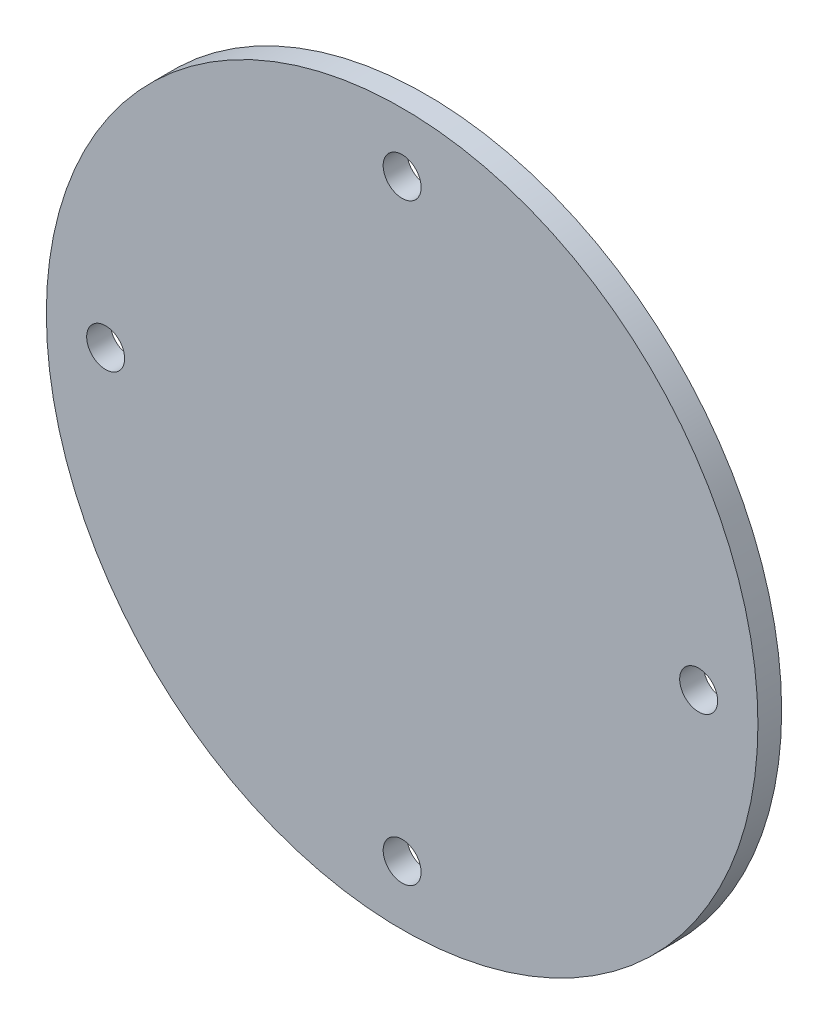
SolidWorks part; units mm, degrees
ref_plane "前视基准面" through (0, 0, 0) normal (0, 0, 1) x (1, 0, 0)
ref_plane "上视基准面" through (0, 0, 0) normal (0, 1, 0) x (1, 0, 0)
ref_plane "右视基准面" through (0, 0, 0) normal (1, 0, 0) x (0, 0, -1)
sketch "草图3" plane through (0, 0, 0) normal (0, 0, 1) x (1, 0, 0)
  line L0 (2.0035, 0) -> (2.0035, 38.673) construction
  circle A0 centre (2.0035, 25) radius 1.6
  circle A3 centre (27.0035, 0) radius 1.6
  circle A4 centre (2.0035, -25) radius 1.6
  circle A5 centre (-22.9965, 0) radius 1.6
  circle A6 centre (2.0035, 0) radius 30
  point P2 (19.826, 16.2278)
  point P8 (-44.3733, 14.57)
  point P11 (2.0035, 23.5)
  point P18 (2.0035, 0)
  point P19 (2.0035, 0)
  point P20 (2.0035, 23.5)
  point P21 (0, 0)
  point P22 (0, 0)
  point P23 (20.847, 23.5)
  dimension "D3" = 3.2
  dimension "D4" = 60
  dimension "D1" = 25
  dimension "D2" = 4
extrude "凸台-拉伸1" add sketch "草图3" along normal blind 2
ref_plane "基准面4" through (13.5017, -13.5017, 0) normal (-0.7071, 0.7071, 0) x (0, 0, 1)
ref_plane "基准面5" through (1.0017, 1.0017, 0) normal (0.7071, 0.7071, 0) x (0, 0, -1)
